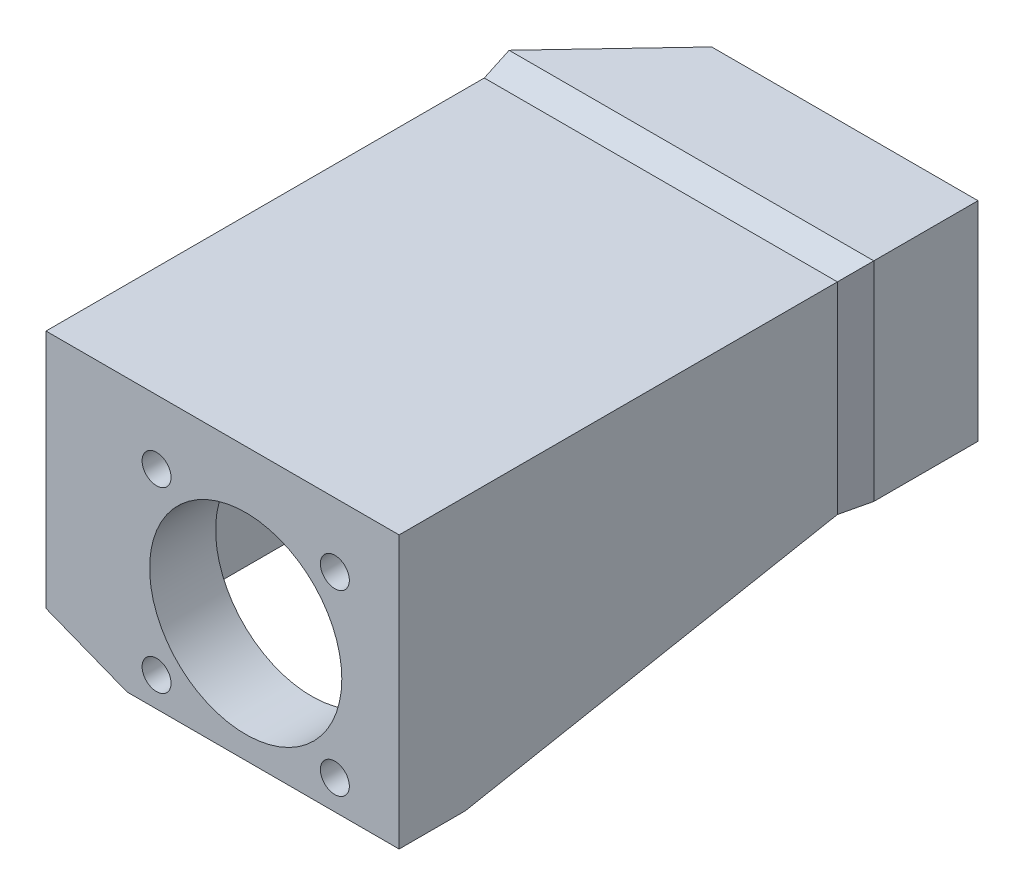
SolidWorks part; units mm, degrees
ref_plane "Front Plane" through (0, 0, 0) normal (0, 0, 1) x (1, 0, 0)
ref_plane "Top Plane" through (0, 0, 0) normal (0, 1, 0) x (1, 0, 0)
ref_plane "Right Plane" through (0, 0, 0) normal (1, 0, 0) x (0, 0, -1)
sketch "Sketch1" plane through (0, 0, 0) normal (0, 0, 1) x (1, 0, 0)
  line L1 (-10.25, 10.25) -> (10.25, 10.25)
  line L2 (-10.25, 10.25) -> (-10.25, -10.25)
  line L3 (-10.25, -10.25) -> (10.25, -10.25)
  line L4 (10.25, 10.25) -> (10.25, -10.25)
  line L5 (-10.25, 10.25) -> (10.25, -10.25) construction
  line L6 (-10.25, -10.25) -> (10.25, 10.25) construction
  point P0 (0, 0)
  dimension "D1" = 20.5
  dimension "D2" = 20.5
extrude "Boss-Extrude1" add sketch "Sketch1" along normal blind 5.7
sketch "Sketch2" plane through (0, 0, 5.7) normal (0, 0, 1) x (1, 0, 0)
  line L0 (-10.25, 0) -> (10.25, 0) construction
  line L1 (-10.25, 10.25) -> (-10.25, -10.25) construction
  line L2 (10.25, -10.25) -> (10.25, 10.25) construction
  line L3 (0, 10.25) -> (0, -10.25) construction
  line L4 (10.25, 10.25) -> (-10.25, 10.25) construction
  line L5 (-10.25, -10.25) -> (10.25, -10.25) construction
  circle A0 centre (0, 0) radius 8.3
  circle A1 centre (-7.7, 7.7) radius 1.25
  circle A2 centre (-7.7, -7.7) radius 1.25
  circle A3 centre (7.7, -7.7) radius 1.25
  circle A4 centre (7.7, 7.7) radius 1.25
  dimension "D1" = 16.6
  dimension "D2" = 2.5
  dimension "D3" = 7.7
  dimension "D4" = 7.7
extrude "Cut-Extrude1" cut sketch "Sketch2" against normal up to next
sketch "Sketch3" plane through (0, 0, 5.7) normal (0, 0, 1) x (1, 0, 0)
  line L0 (-10.25, 10.25) -> (-10.25, 13.25)
  line L1 (-10.25, 13.25) -> (13.25, 13.25)
  line L2 (13.25, 13.25) -> (13.25, -10.25)
  line L3 (13.25, -10.25) -> (10.25, -10.25)
  line L4 (-10.25, 10.25) -> (10.25, 10.25)
  line L5 (10.25, 10.25) -> (10.25, -10.25)
  dimension "D1" = 3
  dimension "D2" = 3
extrude "Boss-Extrude2" add sketch "Sketch3" against normal blind 49
sketch "Sketch5" plane through (0, 0, -43.3) normal (0, 0, -1) x (-1, 0, 0)
  line L0 (-11.75, -10.25) -> (-11.75, 13.25) construction
  line L1 (-10.25, -10.25) -> (-13.25, -10.25) construction
  line L2 (-13.25, 13.25) -> (10.25, 13.25) construction
  line L3 (10.25, 11.75) -> (-13.25, 11.75) construction
  line L4 (10.25, 13.25) -> (10.25, 10.25) construction
  line L5 (-13.25, -10.25) -> (-13.25, 13.25) construction
  circle A2 centre (-11.75, 11.75) radius 0.925
  circle A3 centre (-11.75, -0.75) radius 0.925
  circle A4 centre (2.25, 11.75) radius 0.925
  dimension "D1" = 1.85
  dimension "D2" = 1.85
  dimension "D5" = 1.85
  dimension "D3" = 12.5
  dimension "D4" = 14
extrude "Cut-Extrude2" cut sketch "Sketch5" against normal blind 6
sketch "Sketch6" plane through (0, 0, 5.7) normal (0, 0, 1) x (1, 0, 0)
  line L0 (0, 0) -> (-13.75, 0) construction
  line L1 (-10.25, 13.25) -> (-10.25, -10.25) construction
  line L3 (-17.25, 7.5) -> (-10.25, 7.5)
  line L4 (-17.25, 7.5) -> (-17.25, -7.5)
  line L5 (-17.25, -7.5) -> (-10.25, -7.5)
  line L6 (-10.25, 7.5) -> (-10.25, -7.5)
  line L7 (-17.25, 7.5) -> (-10.25, -7.5) construction
  line L8 (-17.25, -7.5) -> (-10.25, 7.5) construction
  point P5 (-13.75, 0)
  point P10 (-10.25, 0)
  point P11 (-11.6206, 0)
  point P12 (-13.733, -0.7289)
  dimension "D1" = 15
  dimension "D2" = 7
extrude "Boss-Extrude3" add sketch "Sketch6" against normal blind 30
sketch "Sketch7" plane through (0, 0, -24.3) normal (0, 0, -1) x (-1, 0, 0)
  line L1 (17.25, 7.5) -> (14.25, 7.5)
  line L2 (17.25, 7.5) -> (17.25, 1.5)
  line L3 (17.25, 1.5) -> (14.25, 1.5)
  line L4 (14.25, 7.5) -> (14.25, 1.5)
  line L5 (17.25, -1.5) -> (14.25, -1.5)
  line L6 (17.25, -1.5) -> (17.25, -7.5)
  line L7 (17.25, -7.5) -> (14.25, -7.5)
  line L8 (14.25, -1.5) -> (14.25, -7.5)
  point P9 (16.25, -7.5)
  dimension "D1" = 3
  dimension "D2" = 6
  dimension "D3" = 6
  dimension "D4" = 3
extrude "Boss-Extrude4" add sketch "Sketch7" along normal blind 10
sketch "Sketch8" plane through (0, 0, -24.3) normal (0, 0, -1) x (-1, 0, 0)
  line L1 (10.25, 7.5) -> (14.25, 7.5)
  line L2 (10.25, 7.5) -> (10.25, -7.5)
  line L3 (10.25, -7.5) -> (14.25, -7.5)
  line L4 (14.25, 7.5) -> (14.25, -7.5)
extrude "Cut-Extrude3" cut sketch "Sketch8" against normal blind 6
sketch "Sketch9" plane through (0, 0, 5.7) normal (0, 0, 1) x (1, 0, 0)
  line L1 (-10.25, 7.5) -> (-17.25, 7.5)
  line L2 (-10.25, 7.5) -> (-10.25, 13.25)
  line L3 (-10.25, 13.25) -> (-17.25, 13.25)
  line L4 (-17.25, 7.5) -> (-17.25, 13.25)
  dimension "D1" = 5.75
  dimension "D2" = 7
extrude "Boss-Extrude5" add sketch "Sketch9" against normal blind 40
sketch "Sketch10" plane through (0, 0, -43.3) normal (0, 0, -1) x (-1, 0, 0)
  line L0 (-13.25, 13.25) -> (10.25, 13.25) construction
  line L1 (10.25, 10.25) -> (8.75, 10.25)
  line L2 (10.25, 10.25) -> (10.25, 13.25)
  line L3 (10.25, 13.25) -> (8.75, 13.25)
  line L4 (8.75, 10.25) -> (8.75, 13.25)
  dimension "D1" = 1.5
extrude "Cut-Extrude4" cut sketch "Sketch10" against normal blind 9
sketch "Sketch11" plane through (0, 0, -43.3) normal (0, 0, -1) x (-1, 0, 0)
  line L0 (-10.25, 10.25) -> (-10.25, -10.25) construction
  line L1 (-13.25, -10.25) -> (-10.25, -10.25)
  line L2 (-13.25, -10.25) -> (-13.25, -3.75)
  line L3 (-13.25, -3.75) -> (-10.25, -3.75)
  line L4 (-10.25, -10.25) -> (-10.25, -3.75)
  dimension "D1" = 6.5
extrude "Cut-Extrude5" cut sketch "Sketch11" against normal blind 43.3
sketch "Sketch12" plane through (13.25, 0, 0) normal (1, 0, 0) x (0, 0, -1)
  line L0 (43.3, -3.75) -> (0, -10.25)
  line L1 (0, -10.25) -> (0, -3.75)
  line L2 (0, -3.75) -> (43.3, -3.75)
extrude "Boss-Extrude6" add sketch "Sketch12" against normal blind 3
sketch "Sketch13" plane through (0, 0, 5.7) normal (0, 0, 1) x (1, 0, 0)
  line L0 (-17.25, -7.5) -> (-10.25, -10.25)
  line L1 (-10.25, -10.25) -> (-10.25, -7.5)
  line L2 (-10.25, -7.5) -> (-17.25, -7.5)
extrude "Boss-Extrude7" add sketch "Sketch13" against normal blind 5.7
sketch "Sketch14" plane through (0, 0, -34.3) normal (0, 0, -1) x (-1, 0, 0)
  line L1 (10.25, 7.5) -> (14.25, 7.5)
  line L2 (10.25, 7.5) -> (10.25, 10.25)
  line L3 (10.25, 10.25) -> (14.25, 10.25)
  line L4 (14.25, 7.5) -> (14.25, 10.25)
  dimension "D1" = 2.75
  dimension "D2" = 4
extrude "Cut-Extrude6" cut sketch "Sketch14" against normal blind 16
sketch "Sketch18" plane through (0, 0, -18.3) normal (0, 0, -1) x (-1, 0, 0)
  line L0 (10.25, -7.5) -> (14.25, -7.5) construction
  line L1 (10.25, 10.25) -> (11.75, 10.25)
  line L2 (10.25, 10.25) -> (10.25, -7.5)
  line L3 (10.25, -7.5) -> (11.75, -7.5)
  line L4 (11.75, 10.25) -> (11.75, -7.5)
  dimension "D1" = 1.5
extrude "Cut-Extrude7" cut sketch "Sketch18" against normal blind 18.3
sketch "Sketch19" plane through (0, 0, -18.3) normal (0, 0, -1) x (-1, 0, 0)
  line L0 (17.25, 0) -> (11.75, 0) construction
  line L1 (17.25, 1.5) -> (17.25, -1.5) construction
  line L2 (11.75, -7.5) -> (11.75, 10.25) construction
  line L3 (14.25, -7.5) -> (14.25, 10.25) construction
  line L4 (14.25, 3.75) -> (11.75, 3.75)
  line L5 (14.25, 3.75) -> (14.25, 6.75)
  line L6 (14.25, 6.75) -> (11.75, 6.75)
  line L7 (11.75, 3.75) -> (11.75, 6.75)
  dimension "D1" = 3
  dimension "D2" = 3.75
extrude "Boss-Extrude9" add sketch "Sketch19" along normal up to surface (16 mm away) up to face at (-13.4167, 8.3333, -34.3)
chamfer "Chamfer4" distance 2.5 angle 45 2 edges at (-11.75, -1.875, -18.3) (-11.75, 8.5, -18.3)
sketch "Sketch20" plane through (0, 0, -43.3) normal (0, 0, -1) x (-1, 0, 0)
  line L0 (8.75, 13.25) -> (8.75, 14.25)
  line L1 (8.75, 14.25) -> (-14.25, 14.25)
  line L2 (-14.25, 14.25) -> (-14.25, -3.75)
  line L3 (-14.25, -3.75) -> (-13.25, -3.75)
  line L4 (-13.25, -3.75) -> (-13.25, 13.25) construction
  line L5 (-13.25, -3.75) -> (-13.25, 13.25)
  line L6 (-13.25, 13.25) -> (8.75, 13.25)
  line L7 (-13.25, -10.25) -> (-13.25, -3.75) construction
  line L8 (-10.25, -3.75) -> (-10.25, 10.25)
  line L9 (-10.25, 10.25) -> (8.75, 10.25)
  line L10 (8.75, 10.25) -> (8.75, 9.25)
  line L11 (8.75, 9.25) -> (-9.25, 9.25)
  line L12 (-9.25, 9.25) -> (-9.25, -3.75)
  line L13 (-9.25, -3.75) -> (-10.25, -3.75)
  dimension "D1" = 1
  dimension "D2" = 1
  dimension "D3" = 1
  dimension "D4" = 1
extrude "Boss-Extrude10" add sketch "Sketch20" against normal blind 9
sketch "Sketch23" plane through (0, 14.25, 0) normal (0, 1, 0) x (1, 0, 0)
  line L0 (-8.75, 43.3) -> (-17.25, 34.3)
  line L1 (-17.25, 34.3) -> (-8.75, 34.3)
  line L2 (-8.75, 34.3) -> (-8.75, 43.3)
extrude "Boss-Extrude13" add sketch "Sketch23" against normal blind 5
sketch "Sketch24" plane through (13.25, 0, 0) normal (1, 0, 0) x (0, 0, -1)
  line L0 (43.3, -3.75) -> (0, -10.25)
  line L1 (0, -10.25) -> (34.3, -3.75)
  line L2 (34.3, -3.75) -> (43.3, -3.75)
extrude "Cut-Extrude8" cut sketch "Sketch24" against normal blind 3
chamfer "Chamfer7" distance 1 angle 65 4 edges at (-2, 10.25, -34.3) (10.25, 3.25, -34.3) (-2, 13.25, -34.3) (13.25, 4.75, -34.3) first distance on face at (1.75, 5.25, -34.3) first distance on face at (3.4167, 7.9167, -34.3)
